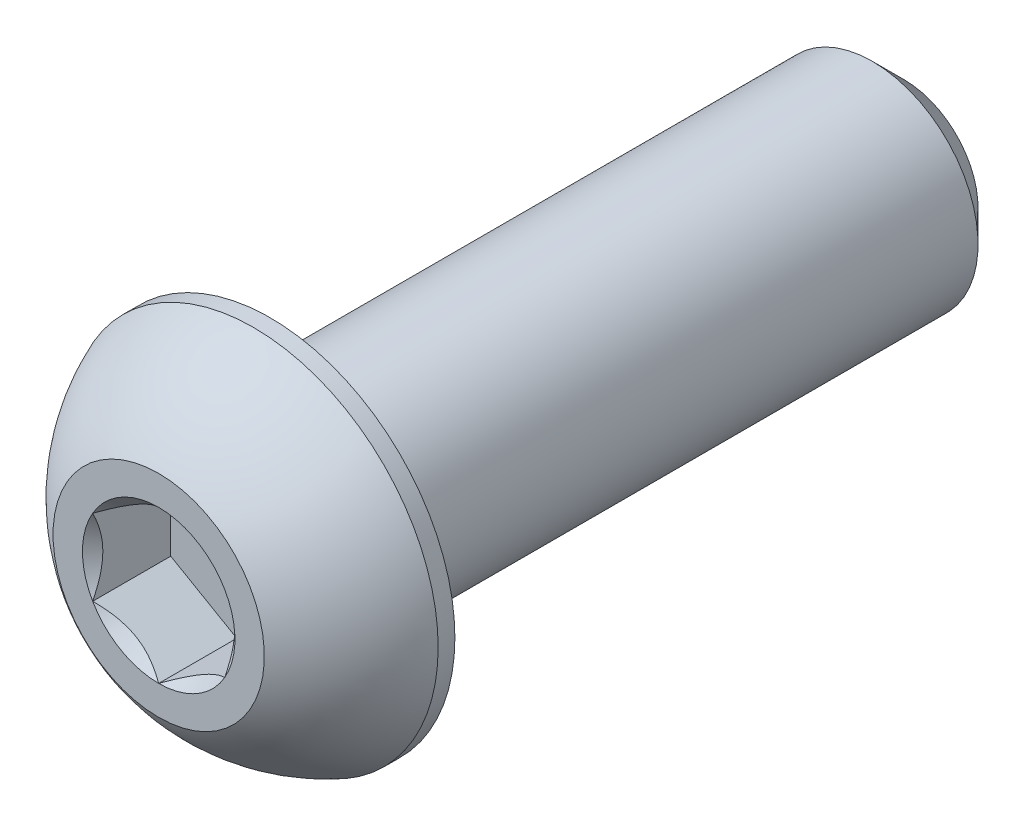
SolidWorks part; units mm, degrees
ref_plane "Front" through (0, 0, 0) normal (0, 0, 1) x (1, 0, 0)
ref_plane "Top" through (0, 0, 0) normal (0, 1, 0) x (1, 0, 0)
ref_plane "Right" through (0, 0, 0) normal (1, 0, 0) x (0, 0, -1)
sketch "Sketch1" plane through (0, 0, 0) normal (1, 0, 0) x (0, 0, -1)
  line L2 (3.3528, 3.175) -> (22.4028, 3.175)
  line L3 (22.4028, 3.175) -> (22.4028, 0)
  line L4 (22.4028, 0) -> (3.3528, 0)
  line L6 (2.8499, 5.5499) -> (3.3528, 5.5499) construction
  line L7 (22.4028, 3.175) -> (22.4028, -3.175) construction
  line L8 (0, 0) -> (3.3528, 0) construction
  line L9 (3.3528, 5.5499) -> (3.3528, -5.5499) construction
  line L11 (3.3528, 3.175) -> (3.3528, 0)
  line L13 (0, 1.9844) -> (0, -1.9844) construction
  line L14 (0, 1.9844) -> (0, 3.175) construction
  arc A3 (0, 3.175) -> (2.8499, 5.5499) centre (5.0603, 0) cw construction
  dimension "D1" = 0.5029
revolve "Revolve1" add sketch "Sketch1" angle 360 mid plane about L4
sketch "Sketch3" plane through (0, 0, -22.4028) normal (0, 0, -1) x (-1, 0, 0)
  circle A0 centre (0, 0) radius 3.175
curve "Helix/Spiral1" pitch 1.27 height 20.32 turns 16
sketch "Sketch2" plane through (0, 0, 0) normal (1, 0, 0) x (0, 0, -1)
  line L0 (22.4028, 3.175) -> (23.514, 3.175)
  line L1 (23.514, 3.175) -> (23.0378, 2.3501)
  line L2 (23.0378, 2.3501) -> (22.879, 2.3501)
  line L3 (22.879, 2.3501) -> (22.4028, 3.175)
  line L4 (22.6409, 2.7626) -> (23.2759, 2.7626) construction
  dimension "D1" = 60
  dimension "D2" = 0.1588
  dimension "D3" = 0.635
chamfer "Chamfer1" distance 0.9525 angle 45 1 edges at (0, 3.175, -22.4028)
sweep "Cut-Sweep1" [suppressed] cut profiles "Sketch2" path "Helix/Spiral1"
sketch "Sketch7" plane through (0, 0, 0) normal (1, 0, 0) x (0, 0, -1)
  line L6 (2.8499, 5.5499) -> (3.3528, 5.5499) construction
  line L8 (0, 0) -> (3.3528, 0) construction
  line L11 (3.3528, 5.5499) -> (3.3528, -5.5499) construction
  line L12 (2.8499, 5.5499) -> (3.3528, 5.5499)
  line L13 (0, 0) -> (3.3528, 0)
  line L14 (0, 1.9844) -> (0, -1.9844) construction
  line L15 (3.3528, 5.5499) -> (3.3528, 0)
  line L16 (0, 3.175) -> (0, 0)
  arc A2 (2.8499, 5.5499) -> (0, 3.175) centre (5.0603, 0) ccw construction
  arc A3 (2.8499, 5.5499) -> (0, 3.175) centre (5.0603, 0) ccw
revolve "Revolve2" add sketch "Sketch7" angle 360 mid plane about L13
sketch "Sketch5" plane through (0, 0, 0) normal (0, 0, 1) x (1, 0, 0)
  line L1 (1.9844, -1.1457) -> (1.9844, 1.1457)
  line L2 (1.9844, 1.1457) -> (0, 2.2914)
  line L3 (0, 2.2914) -> (-1.9844, 1.1457)
  line L4 (-1.9844, 1.1457) -> (-1.9844, -1.1457)
  line L5 (-1.9844, -1.1457) -> (0, -2.2914)
  line L6 (0, -2.2914) -> (1.9844, -1.1457)
  circle A0 centre (0, 0) radius 1.9844 construction
extrude "Cut-Extrude2" cut sketch "Sketch5" against normal blind 2.347
sketch "Sketch6" plane through (0, 0, 0) normal (0, 0, 1) x (1, 0, 0)
  circle A0 centre (0, 0) radius 2.2914
extrude "Cut-Extrude3" cut sketch "Sketch6" against normal blind 2.347 draft 45
sketch "Sketch9" [suppressed] plane through (0, 0, -3.3528) normal (0, 0, 1) x (1, 0, 0)
  circle A2 centre (0, 0) radius 3.175
extrude "Boss-Extrude2" [suppressed] add sketch "Sketch9" against normal offset from surface (12.7 mm away) 22.225 up to face at (0, 2.2225, -22.4028)
sketch "Sketch10" plane through (0, 0, 0) normal (1, 0, 0) x (0, 0, -1)
  line L0 (22.4028, 3.175) -> (22.4028, -3.175) construction
  point P0 (20.4978, -3.175)
  dimension "D1" = 1.905
equation "\"D3@Helix/Spiral1\" = \"Lg@Sketch1\" + \"D4@Helix/Spiral1\""
equation "\"D2@Sketch2\" = \"D4@Helix/Spiral1\" * .125"
equation "\"D3@Sketch2\" = \"D4@Helix/Spiral1\" * .5"
equation "\"D1@Chamfer1\" = \"D4@Helix/Spiral1\" * .75"
equation "\"D1@Cut-Extrude2\" = \"Head Ht@Sketch1\" * .7"
equation "\"D1@Sketch1\" = \"Head Ht@Sketch1\" * .15"
equation "\"D1@Sketch10\" = \"D4@Helix/Spiral1\" * 1.5"
equation "\"D1@Cut-Extrude3\" = \"D1@Cut-Extrude2\""
